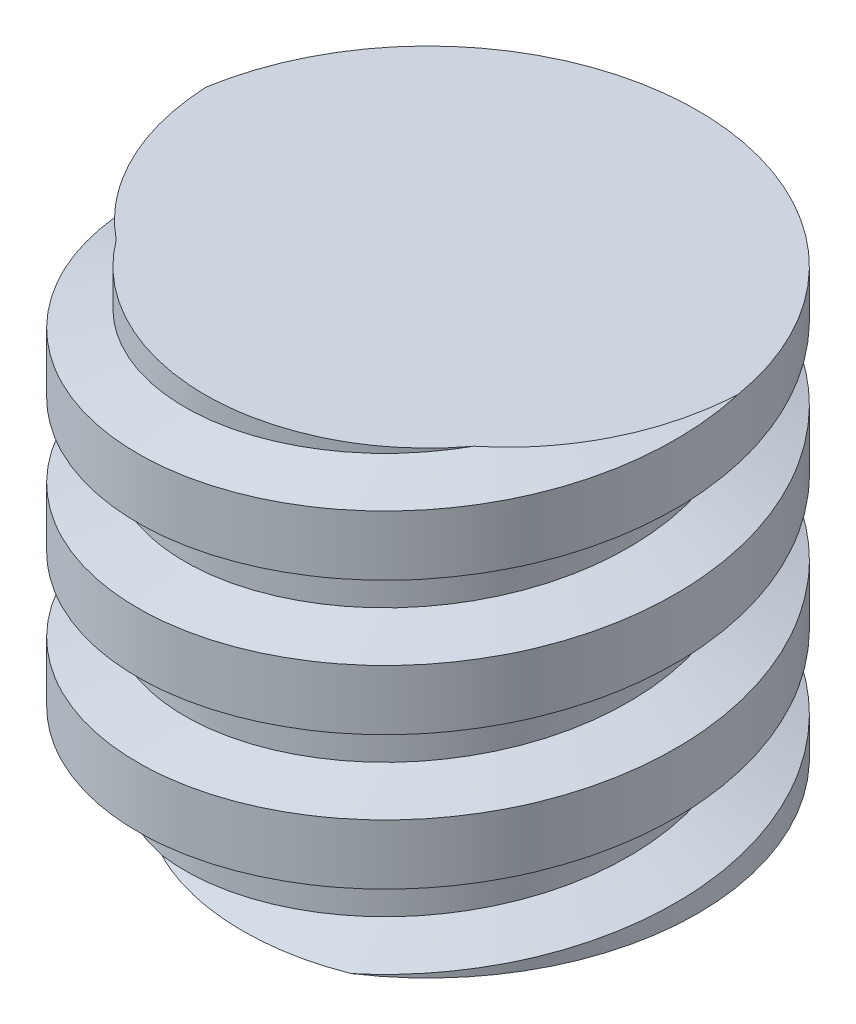
SolidWorks part; units mm, degrees
ref_plane "Спереди" through (0, 0, 0) normal (0, 0, 1) x (1, 0, 0)
ref_plane "Сверху" through (0, 0, 0) normal (0, 1, 0) x (1, 0, 0)
ref_plane "Справа" through (0, 0, 0) normal (1, 0, 0) x (0, 0, -1)
sketch "Эскиз3" plane through (0, 0, 0) normal (0, 0, 1) x (1, 0, 0)
  line L0 (0, 0) -> (0, 16.0133) construction
  line L1 (0, 0) -> (9.5, 0)
  line L2 (9.5, 0) -> (9.5, 15)
  line L3 (9.5, 15) -> (0, 15)
  line L4 (0, 15) -> (0, 0)
  line L5 (0, 16.0133) -> (15.8419, 16.0133) construction
  line L6 (0, 0) -> (0, 40.7619) construction
  dimension "D1" = 9.5
  dimension "D2" = 15
revolve "Повернуть1" add sketch "Эскиз3" angle 360 about L0
sketch "Эскиз6" plane through (0, 15, 0) normal (0, 1, 0) x (1, 0, 0)
  circle A1 centre (0, 0) radius 9.5
  circle A2 centre (0, 0) radius 9.5
  dimension "D1" = 0
curve "Спираль1" pitch 4.712 height 36.518 turns 7.75
sketch "Эскиз7" plane through (0, 0, 0) normal (1, 0, 0) x (0, 0, -1)
  line L0 (-9.5, 12.8871) -> (-9.5, -1.6217) construction
  line L1 (-9.5, 15) -> (-9.5, 0) construction
  line L2 (-9.5, 16.3) -> (-9.5, 13.7) construction
  line L4 (-7.85, 14.3006) -> (-7.85, 15.6994)
  line L5 (-7.85, 15.6994) -> (-11.15, 16.9006)
  line L6 (-11.15, 16.9006) -> (-11.15, 13.0994)
  line L7 (-11.15, 13.0994) -> (-7.85, 14.3006)
  line L9 (-11.15, 15) -> (-1.3827, 15) construction
  point P13 (-9.5, 15)
  dimension "D1" = 3.3
  dimension "D2" = 20
  dimension "D3" = 2.6
sweep "Вырез-По траектории1" cut profiles "Эскиз7" path "Спираль1" align with end faces yes
